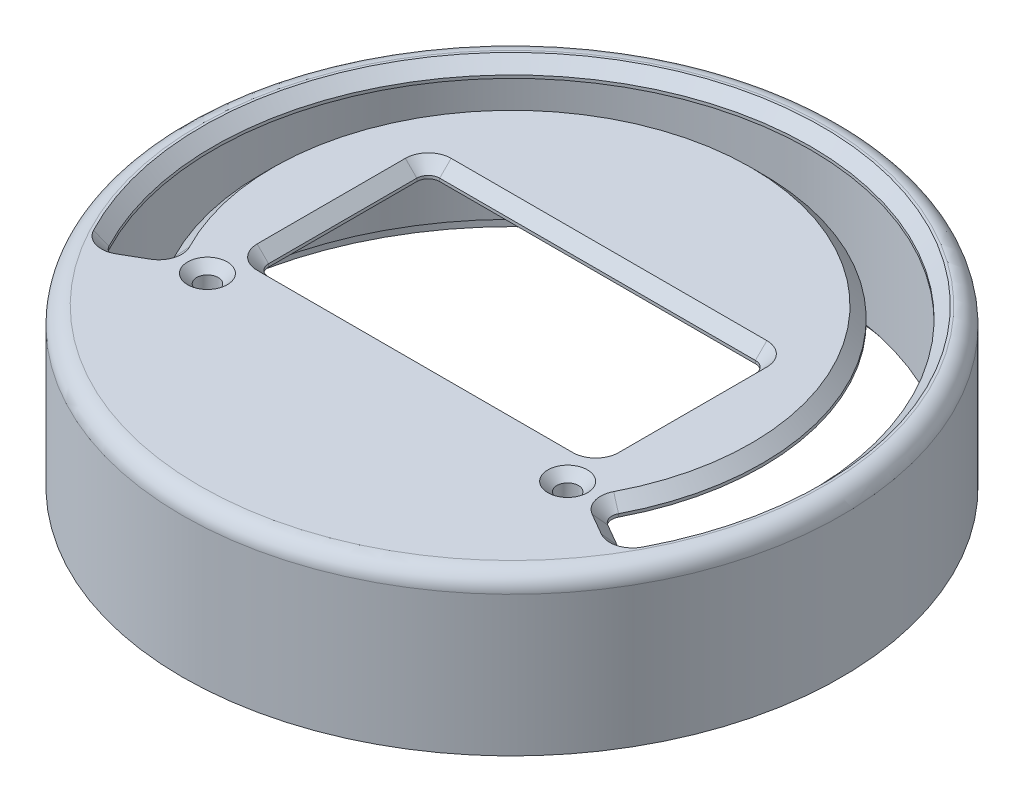
SolidWorks part; units mm, degrees
ref_plane "Front Plane" through (0, 0, 0) normal (0, 0, 1) x (1, 0, 0)
ref_plane "Top Plane" through (0, 0, 0) normal (0, 1, 0) x (1, 0, 0)
ref_plane "Right Plane" through (0, 0, 0) normal (1, 0, 0) x (0, 0, -1)
sketch "Sketch1" plane through (0, 0, 0) normal (0, 1, 0) x (1, 0, 0)
  line L0 (18.8, 9.5) -> (-18.8, -9.5) construction
  line L1 (20, -13.8201) -> (-20, -13.8201) construction
  line L2 (-28.7061, -16.5735) -> (-24.0868, -13.9065)
  line L3 (24.0868, -13.9065) -> (28.7061, -16.5735)
  line L4 (-28.7061, -16.5735) -> (28.7061, -16.5735) construction
  line L5 (0, 0) -> (0, -16.5735) construction
  line L6 (-24.0868, -13.9065) -> (0, 0) construction
  line L7 (0, 0) -> (24.0868, -13.9065) construction
  line L8 (-18.8, 9.5) -> (-18.8, -9.5)
  line L9 (-18.8, -9.5) -> (18.8, -9.5)
  line L10 (18.8, -9.5) -> (18.8, 9.5)
  line L11 (18.8, 9.5) -> (-18.8, 9.5)
  arc A0 (-22.3357, -16.5735) -> (22.3357, -16.5735) centre (0, 0) ccw construction
  circle A1 centre (0, 0) radius 36.5951
  arc A2 (28.7061, -16.5735) -> (-28.7061, -16.5735) centre (0, 0) ccw
  arc A3 (24.0868, -13.9065) -> (-24.0868, -13.9065) centre (0, 0) ccw
  arc A4 (-24.0868, -13.9065) -> (-22.3357, -16.5735) centre (0, 0) ccw construction
  arc A5 (22.3357, -16.5735) -> (24.0868, -13.9065) centre (0, 0) ccw construction
  arc A6 (-28.7061, -16.5735) -> (28.7061, -16.5735) centre (0, 0) ccw construction
  circle A7 centre (-20, -13.8201) radius 2.2225 construction
  circle A8 centre (20, -13.8201) radius 2.2225 construction
  circle A9 centre (0, 0) radius 34.1249 construction
  circle A10 centre (0, 0) radius 30.48 construction
  point P18 (0, -13.8201)
  point P21 (-26.3965, -15.24)
  dimension "D3" = 5.334
  dimension "D4" = 73.1901
  dimension "D7" = 4.445
  dimension "D10" = 68.2498
  dimension "D11" = 60.96
  dimension "D2" = 120
  dimension "D5" = 37.6
  dimension "D6" = 19
  dimension "D8" = 40
  dimension "D9" = 13.8201
extrude "Boss-Extrude1" add sketch "Sketch1" along normal blind 1.6
sketch "Sketch2" plane through (0, 0, 0) normal (0, -1, 0) x (1, 0, 0)
  circle A0 centre (20, 13.8201) radius 2.2225 construction
  circle A1 centre (-20, 13.8201) radius 2.2225 construction
  circle A2 centre (0, 0) radius 36.5951 construction
  circle A3 centre (0, 0) radius 34.1249 construction
  circle A4 centre (20, 13.8201) radius 2.2225
  circle A5 centre (-20, 13.8201) radius 2.2225
  circle A6 centre (0, 0) radius 36.5951
  circle A7 centre (0, 0) radius 34.1249
  circle M5 centre (0, 0) radius 36.5951
extrude "Boss-Extrude2" add sketch "Sketch2" along normal blind 14.2494 contours A5 | A4 | A7 M5 region at (20, 0, 13.8201) region at (-20, 0, 13.8201) region at (-35.56, 0, 0)
hole_wizard "CSK for M2 Flat Head Machine Screw1" positions "Sketch3" profile "Sketch4" countersink size "M2" standard "ANSI Metric" end condition up to next
sketch "Sketch3" plane through (0, 1.6, 0) normal (0, 1, 0) x (1, 0, 0)
  point P0 (-20, -13.8201)
  point P3 (20, -13.8201)
sketch "Sketch4" plane through (-20, 1.6, 13.8201) normal (1, 0, 0) x (0, 0, 1)
  line L0 (0, 0) -> (0, 15.8494)
  line L1 (0, 15.8494) -> (1.2, 15.8494)
  line L2 (1.2, 15.8494) -> (1.2, 1)
  line L3 (1.2, 1) -> (2.2, 0)
  line L5 (2.2, 0) -> (0, 0)
  line L6 (-1.2, 1) -> (-2.2, 0) construction
  line L11 (0, -6.35) -> (0, 107.95) construction
  dimension "Thru Hole Dia." = 2.4
  dimension "Thru Hole Depth" = 15.8494
  dimension "Near C'Sink Dia." = 4.4
  dimension "Near C'Sink Angle" = 90
fillet "Fillet1" radius 1.27 8 edges at (24.0868, 0.8, 13.9065) (28.7061, 0.8, 16.5735) (-28.7061, 0.8, 16.5735) (-24.0868, 0.8, 13.9065) (-18.8, 0.8, 9.5) (18.8, 0.8, 9.5) (18.8, 0.8, -9.5) (-18.8, 0.8, -9.5)
sketch "Sketch5" plane through (0, -14.2494, 0) normal (0, -1, 0) x (1, 0, 0)
  circle A1 centre (0, 0) radius 36.5951
  circle A2 centre (0, 0) radius 36.5951
  circle A3 centre (0, 0) radius 35.3949
  dimension "D2" = 70.7898
  dimension "D1" = 0
extrude "Boss-Extrude3" add sketch "Sketch5" along normal blind 1.6
chamfer "Chamfer2" distance 1.27 angle 45 16 edges at (0, 1.6, -27.813) (24.5783, 1.6, 13.7832) (-24.5783, 1.6, 13.7832) (26.3735, 1.6, 15.2267) (-26.3735, 1.6, 15.2267) (28.5725, 1.6, 16.0459) (-28.5725, 1.6, 16.0459) (0, 1.6, -33.147) (18.8, 1.6, 0) (18.428, 1.6, -9.128) (18.428, 1.6, 9.128) (0, 1.6, -9.5) (0, 1.6, 9.5) (-18.428, 1.6, 9.128) (-18.8, 1.6, 0) (-18.428, 1.6, -9.128)
fillet "Fillet2" radius 1.905 1 edges at (0, 1.6, 36.5951)
